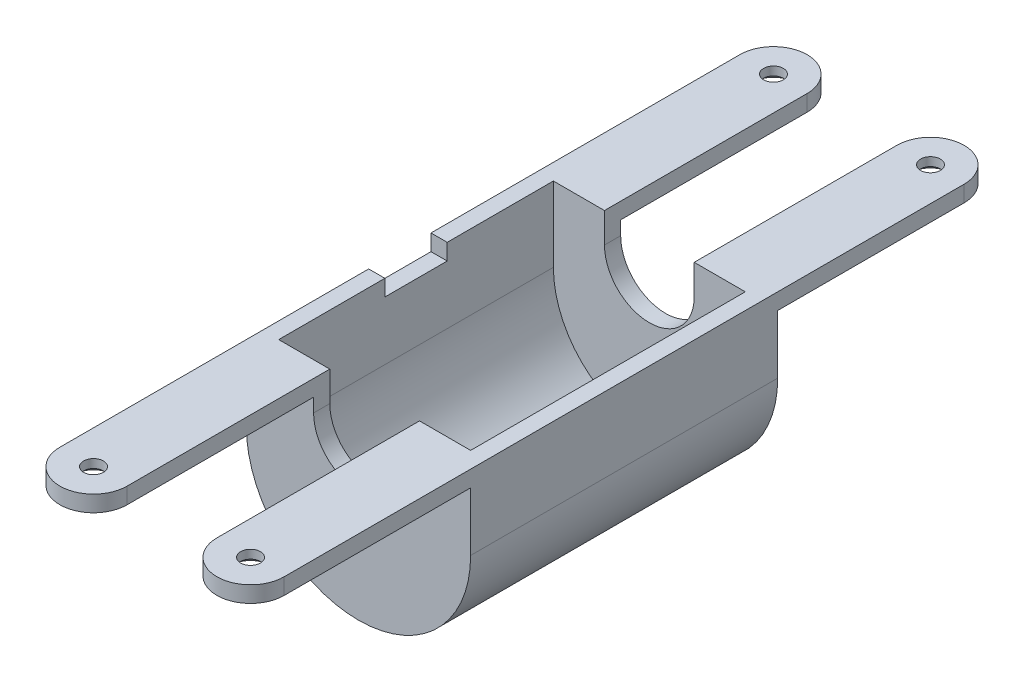
SolidWorks part; units mm, degrees
ref_plane "Front Plane" through (0, 0, 0) normal (0, 0, 1) x (1, 0, 0)
ref_plane "Top Plane" through (0, 0, 0) normal (0, 1, 0) x (1, 0, 0)
ref_plane "Right Plane" through (0, 0, 0) normal (1, 0, 0) x (0, 0, -1)
sketch "Sketch1" plane through (0, 0, 0) normal (0, 0, 1) x (1, 0, 0)
  line L0 (0, 58.7375) -> (0, -57.583) construction
  line L1 (22.86, 38.1) -> (57.15, 38.1)
  line L2 (-22.86, 38.1) -> (-57.15, 38.1)
  line L3 (57.15, 38.1) -> (57.15, 0)
  line L4 (-57.15, 38.1) -> (-57.15, 0)
  line L5 (22.86, 38.1) -> (22.86, 22.86)
  line L6 (-22.86, 38.1) -> (-22.86, 22.86)
  arc A0 (57.15, 0) -> (-57.15, 0) centre (0, 0) cw
  arc A1 (22.86, 22.86) -> (-22.86, 22.86) centre (0, 22.86) cw
  point P13 (0, 0)
  point P14 (0, 0)
  point P15 (0, 0)
  dimension "D1" = 38.1
  dimension "D3" = 57.15
  dimension "D2" = 34.29
extrude "Boss-Extrude2" add sketch "Sketch1" along normal mid plane 156.464
shell "Shell1" thickness 8.255 removed face at (22.86, 30.48, 0) removed face at (-22.86, 30.48, 0) removed face at (0, 11.43, 0) removed face at (40.005, 38.1, 0) removed face at (-40.005, 38.1, 0)
sketch "Sketch2" plane through (-48.895, 0, 0) normal (1, 0, 0) x (0, 0, -1)
  line L0 (-15.875, 38.1) -> (-15.875, 29.845)
  line L1 (-69.977, 38.1) -> (69.977, 38.1) construction
  line L2 (-15.875, 29.845) -> (15.875, 29.845)
  line L3 (15.875, 29.845) -> (15.875, 38.1)
  line L4 (15.875, 38.1) -> (-15.875, 38.1)
  point P4 (0, 38.1)
  dimension "D1" = 31.75
  dimension "D2" = 8.255
extrude "Cut-Extrude1" cut sketch "Sketch2" against normal blind 8.255
sketch "Sketch3" plane through (0, 0, 78.232) normal (0, 0, 1) x (1, 0, 0)
  line L0 (-57.15, 29.845) -> (-22.86, 29.845)
  line L1 (-22.86, 22.86) -> (-22.86, 38.1) construction
  line L2 (-22.86, 29.845) -> (-22.86, 38.1)
  line L3 (-22.86, 38.1) -> (-57.15, 38.1)
  line L4 (-57.15, 38.1) -> (-57.15, 29.845)
extrude "Boss-Extrude3" add sketch "Sketch3" along normal blind 112.141 separate body
sketch "Sketch5" plane through (0, 38.1, 0) normal (0, 1, 0) x (1, 0, 0)
  line L0 (-57.15, -190.373) -> (-57.15, -78.232) construction
  line L1 (-22.86, -190.373) -> (-22.86, -78.232) construction
  line L2 (-22.86, -190.373) -> (-57.15, -190.373) construction
  arc A0 (-57.15, -173.228) -> (-22.86, -173.228) centre (-40.005, -173.228) ccw
extrude "Cut-Extrude2" cut sketch "Sketch5" against normal through all and the other way through all flip side to cut
hole_wizard "CSK for 3/8 Flat Head Machine Screw (100)1" positions "Sketch6" profile "Sketch7" countersink size "3/8" standard "ANSI Inch" end condition through all
sketch "Sketch6" plane through (0, 29.845, 0) normal (0, -1, 0) x (-1, 0, 0)
  arc A0 (22.86, -173.228) -> (57.15, -173.228) centre (40.005, -173.228) ccw construction
  point P0 (40.005, -173.228)
  point P5 (0, 0)
sketch "Sketch7" plane through (-40.005, 29.845, 173.228) normal (1, 0, 0) x (0, 0, -1)
  line L0 (0, 0) -> (0, 8.255)
  line L1 (0, 8.255) -> (5.0419, 8.255)
  line L2 (5.0419, 8.255) -> (5.0419, 3.8896)
  line L3 (5.0419, 3.8896) -> (9.6774, 0)
  line L5 (9.6774, 0) -> (0, 0)
  line L6 (-5.0419, 3.8896) -> (-9.6774, 0) construction
  line L11 (0, -6.35) -> (0, 107.95) construction
  dimension "Thru Hole Dia." = 10.0838
  dimension "Thru Hole Depth" = 8.255
  dimension "Near C'Sink Dia." = 19.3548
  dimension "Near C'Sink Angle" = 100
mirror "Mirror2" about plane through (0, 0, 0) normal (1, 0, 0) of bodies 107
mirror "Mirror3" about plane through (0, 0, 0) normal (0, 0, 1) of bodies 107 108
combine bodies "Combine2" operation type add bodies to combine 107 108 109 110 103
